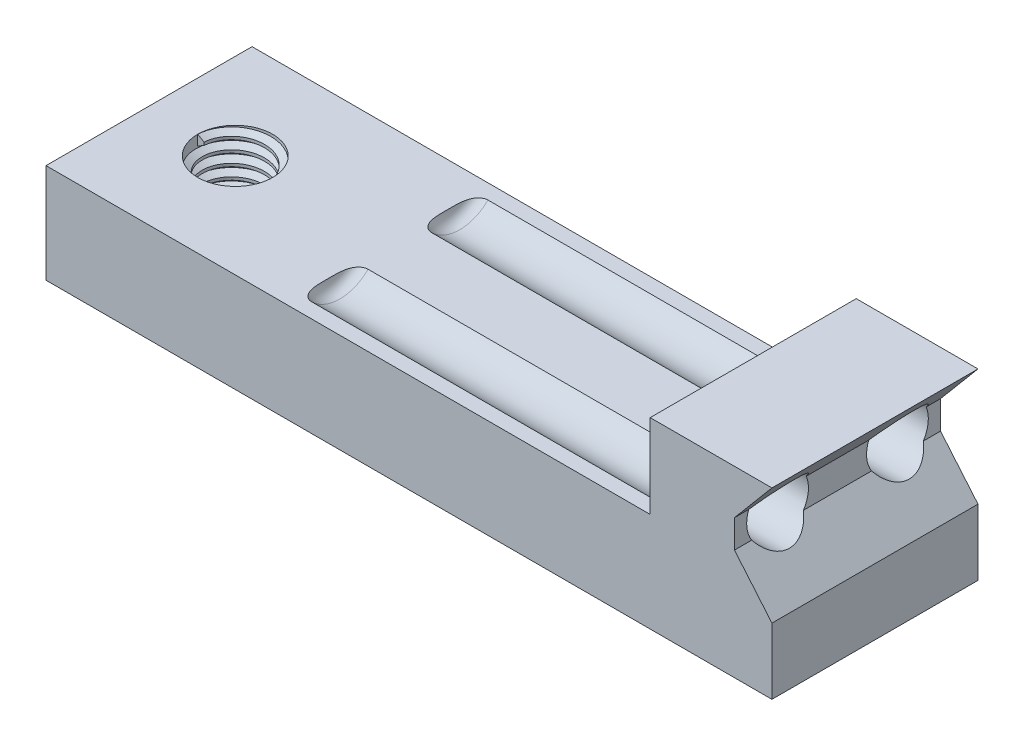
SolidWorks part; units mm, degrees
ref_plane "Front Plane" through (0, 0, 0) normal (0, 0, 1) x (1, 0, 0)
ref_plane "Top Plane" through (0, 0, 0) normal (0, 1, 0) x (1, 0, 0)
ref_plane "Right Plane" through (0, 0, 0) normal (1, 0, 0) x (0, 0, -1)
sketch "Sketch1" plane through (0, 0, 0) normal (0, 1, 0) x (1, 0, 0)
  line L0 (0, 0) -> (77.5005, 0)
  line L1 (77.5005, 0) -> (77.5005, 21.9989)
  line L2 (77.5005, 21.9989) -> (0, 21.9989)
  line L3 (0, 21.9989) -> (0, 0)
  dimension "D1" = 77.5005
  dimension "D2" = 21.9989
extrude "Boss-Extrude1" add sketch "Sketch1" along normal blind 19.5504
sketch "Sketch3" plane through (0, 19.5504, 0) normal (0, 1, 0) x (1, 0, 0)
  line L0 (0, 21.9989) -> (64.5008, 21.9989)
  line L1 (77.5005, 21.9989) -> (0, 21.9989) construction
  line L2 (64.5008, 21.9989) -> (64.5008, 0)
  line L3 (0, 0) -> (77.5005, 0) construction
  line L4 (64.5008, 0) -> (0, 0)
  line L5 (0, 0) -> (0, 21.9989)
  dimension "D1" = 64.5008
extrude "Cut-Extrude1" cut sketch "Sketch3" against normal blind 8.951
sketch "Sketch4" plane through (77.5005, 0, 0) normal (1, 0, 0) x (0, 0, -1)
  line L0 (0, 19.5504) -> (21.9989, 19.5504) construction
  line L1 (21.9989, 19.5504) -> (21.9989, 0) construction
  line L2 (0, 19.5504) -> (0, 0) construction
  circle A0 centre (4.5999, 13.5992) radius 3.2969
  circle A1 centre (17.399, 13.5992) radius 3.2969
  dimension "D5" = 6.5938
  dimension "D6" = 6.5938
  dimension "D1" = 5.9512
  dimension "D2" = 5.9512
  dimension "D3" = 4.5999
  dimension "D4" = 4.5999
extrude "Cut-Extrude2" cut sketch "Sketch4" against normal blind 38.1
sketch "Sketch5" plane through (64.5008, 0, 0) normal (-1, 0, 0) x (0, 0, 1)
  circle A0 centre (-17.399, 13.5992) radius 4.2494
  circle A1 centre (-4.5999, 13.5992) radius 4.2494
  dimension "D1" = 8.4988
  dimension "D2" = 8.4988
extrude "Cut-Extrude3" cut sketch "Sketch5" against normal blind 2.9997 and the other way blind 38.9992
fillet "Fillet3" radius 1.27 2 edges at (25.5016, 9.3497, -4.5999) (25.5016, 9.3497, -17.399)
sketch "Sketch6" plane through (0, 0, 0) normal (0, 0, 1) x (1, 0, 0)
  line L0 (77.5005, 7.051) -> (73.5, 11.8008)
  line L1 (77.5005, 19.5504) -> (77.5005, 0) construction
  line L2 (73.5, 11.8008) -> (73.5, 14.8006)
  line L3 (73.5, 14.8006) -> (77.5005, 19.5504)
  line L4 (77.5005, 19.5504) -> (77.5005, 7.051)
  dimension "D1" = 7.051
  dimension "D2" = 4.0005
  dimension "D3" = 4.7498
  dimension "D4" = 2.9997
extrude "Cut-Extrude4" cut sketch "Sketch6" against normal through all
sketch "Sketch7" plane through (0, 10.5994, 0) normal (0, 1, 0) x (1, 0, 0)
  line L0 (0, 21.9989) -> (0, 0) construction
  line L1 (0, 0) -> (64.5008, 0) construction
  circle A0 centre (9.1999, 11.0007) radius 4
  dimension "D3" = 8
  dimension "D1" = 9.1999
  dimension "D2" = 11.0007
extrude "Cut-Extrude5" cut sketch "Sketch7" against normal through all
thread "Thread1" pitch 1.25 method extrude profile "Thread Profile1" start angle 0, offset 0, length 9.4996, pitch 1.25, diameter 8
ref_plane "Plane1" through (5.1999, 10.5994, -11.0007) normal (0, 0, 1) x (-1, 0, 0)
sketch "Thread Profile1" plane through (5.1999, 10.5994, -11.0007) normal (0, 0, 1) x (-1, 0, 0)
  line L0 (0, 0) -> (0, 1.25) construction
  line L11 (0, 0) -> (0, 1.0937)
  line L12 (0, 1.0937) -> (-0.6766, 0.7031)
  line L13 (-0.6766, 0.7031) -> (-0.6766, 0.3906)
  line L15 (-0.6766, 0.3906) -> (0, 0)
  line L17 (-0.6766, 0.5469) -> (0, 0.5469) construction
  point P2 (0, 0)
  dimension "Pitch" = 1.25
  dimension "Profile_Angle" = 60
  dimension "Profile_Land" = 0.3125
  dimension "Profile_Height" = 0.6766
